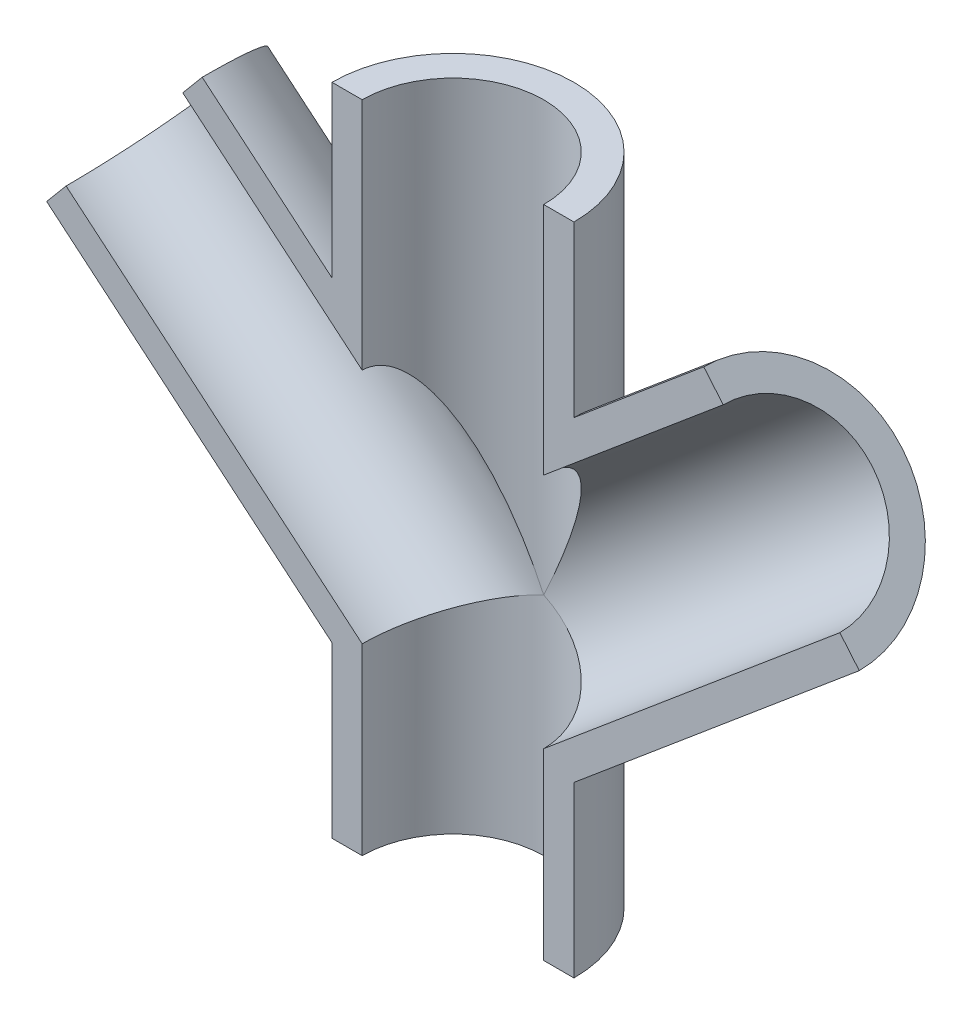
SolidWorks part; units mm, degrees
ref_plane "Спереди" through (0, 0, 0) normal (0, 0, 1) x (1, 0, 0)
ref_plane "Сверху" through (0, 0, 0) normal (0, 1, 0) x (1, 0, 0)
ref_plane "Справа" through (0, 0, 0) normal (1, 0, 0) x (0, 0, -1)
sketch "Эскиз3" plane through (0, 0, 0) normal (0, 0, 1) x (1, 0, 0)
  line L1 (0, -50) -> (0, 50) construction
  line L3 (-5, 7) -> (-16.7902, 16.8931)
  line L4 (-16.7902, 16.8931) -> (-10.3623, 24.5536)
  line L5 (-10.3623, 24.5536) -> (-5, 20.0541)
  line L6 (-5, 20.0541) -> (-5, 27.0541)
  line L7 (-5, 27.0541) -> (5, 27.0541)
  line L8 (0, 27.0541) -> (0, 0) construction
  line L9 (5, 20.0541) -> (5, 27.0541)
  line L10 (10.3623, 24.5536) -> (5, 20.0541)
  line L11 (16.7902, 16.8931) -> (10.3623, 24.5536)
  line L12 (5, 7) -> (16.7902, 16.8931)
  line L17 (-5, 7) -> (-5, 0)
  line L18 (-5, 0) -> (5, 0)
  line L19 (5, 7) -> (5, 0)
  point P1 (-12.0711, 20.954)
  point P15 (0, 0)
  point P16 (-11.8734, 28.1421)
  point P20 (-10.2307, 26.3728)
  dimension "D1" = 7
  dimension "D3" = 7
  dimension "D4" = 50
  dimension "D5" = 10
extrude "Основа тройника" add sketch "Эскиз3" along normal mid plane 10
sketch "Эскиз4" plane through (0, 27.0541, 0) normal (0, 1, 0) x (-1, 0, 0)
  line L3 (5, 5) -> (5, -5) construction
  line L5 (-5, 5) -> (5, 5) construction
  circle A0 centre (0, 0) radius 3.75
  point P8 (5, 0)
  point P14 (0, 5)
  dimension "D1" = 7.5
extrude "Центральный вырез под гофру" cut sketch "Эскиз4" against normal through all
sketch "Эскиз5" plane through (-18.1711, 15.2474, 0) normal (-0.766, 0.6428, 0) x (0, 0, 1)
  line L0 (0, 20.7246) -> (0, 0) construction
  line L1 (5, 12.1484) -> (5, 2.1484) construction
  circle A0 centre (0, 7.1484) radius 3.75
  point P7 (5, 7.1484)
  dimension "D1" = 7.5
extrude "Боковой вырез под гофру" cut sketch "Эскиз5" against normal up to next
mirror "Зеркальное отражение1" about plane through (0, 0, 0) normal (1, 0, 0) of "Боковой вырез под гофру"
sketch "Эскиз9" plane through (0, 0, 0) normal (0, -1, 0) x (1, 0, 0)
  circle A0 centre (0, 0) radius 5.25
  dimension "D1" = 10.5
extrude "Под толстую гофру" [suppressed] cut sketch "Эскиз9" against normal blind 8
draft "Уклон2" [suppressed] type of draft neutral plane draft angle 4 neutral plane "Сверху" faces to draft 2 parameters "D1"=4
fillet "Скругление8" radius 5 16 edges at (7.6812, 22.3038, -5) (5, 23.5541, -5) (-5, 23.5541, -5) (-7.6812, 22.3038, -5) (-10.8951, 11.9466, -5) (-5, 3.5, -5) (5, 3.5, -5) (10.8951, 11.9466, -5) (-5, 3.5, 5) (5, 3.5, 5) (10.8951, 11.9466, 5) (7.6812, 22.3038, 5) (5, 23.5541, 5) (-5, 23.5541, 5) (-7.6812, 22.3038, 5) (-10.8951, 11.9466, 5)
split "Разделит пополам" trim tools "Спереди" bodies to split 108 resulting bodies 114
